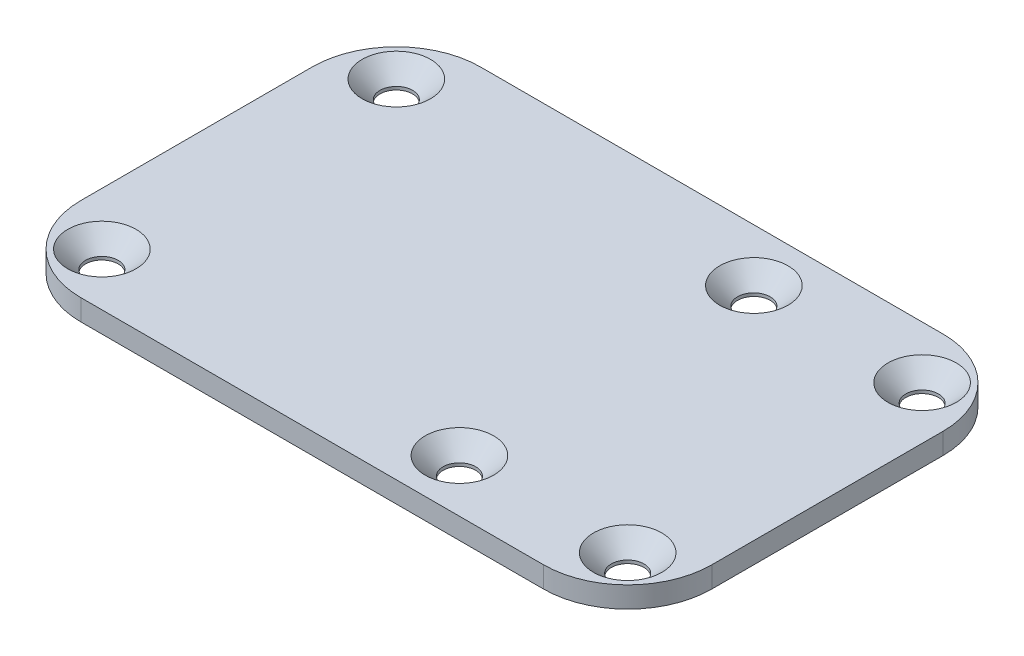
SolidWorks part; units mm, degrees
material "6063-T6"
ref_plane "Front Plane" through (0, 0, 0) normal (0, 0, 1) x (1, 0, 0)
ref_plane "Top Plane" through (0, 0, 0) normal (0, 1, 0) x (1, 0, 0)
ref_plane "Right Plane" through (0, 0, 0) normal (1, 0, 0) x (0, 0, -1)
sketch "Sketch1" plane through (0, 0, 0) normal (0, 1, 0) x (1, 0, 0)
  line L1 (22, -19) -> (-22, -19)
  line L2 (30, -11) -> (30, 11)
  line L3 (22, 19) -> (-22, 19)
  line L4 (-30, -11) -> (-30, 11)
  line L5 (30, -19) -> (-30, 19) construction
  line L6 (30, 19) -> (-30, -19) construction
  arc A0 (30, 11) -> (22, 19) centre (22, 11) ccw
  arc A1 (22, -19) -> (30, -11) centre (22, -11) ccw
  arc A2 (-22, -19) -> (-30, -11) centre (-22, -11) cw
  arc A3 (-22, 19) -> (-30, 11) centre (-22, 11) ccw
  point P0 (0, 0)
  dimension "D3" = 8
  dimension "D1" = 60
  dimension "D2" = 38
extrude "Base" add sketch "Sketch1" along normal blind 2
hole_wizard "Ø3.1 (3.1) Diameter Hole1" positions "Location" profile "Hole" hole size "Ø3.1" standard "ANSI Metric" end condition through all
sketch "Location" plane through (0, 2, 0) normal (0, -1, 0) x (-1, 0, 0)
  line L4 (-33.1926, 0) -> (33.4931, 0) construction
  line L6 (0, 17.9223) -> (0, -17.6691) construction
  point P0 (-25, 14)
  point P2 (-25, -14)
  point P4 (25, -14)
  point P6 (25, 14)
  point P29 (-9, 14)
  point P31 (-9, -14)
  dimension "D1" = 28
  dimension "D2" = 25
  dimension "D3" = 25
  dimension "D4" = 16
sketch "Hole" plane through (25, 2, -14) normal (1, 0, 0) x (0, 0, 1)
  line L0 (0, 0) -> (0, 2)
  line L1 (0, 2) -> (1.55, 2)
  line L2 (1.55, 2) -> (1.55, 1.7)
  line L3 (1.55, 1.7) -> (3.25, 0)
  line L5 (3.25, 0) -> (0, 0)
  line L6 (-1.55, 1.7) -> (-3.25, 0) construction
  line L11 (0, -6.35) -> (0, 107.95) construction
  dimension "Thru Hole Dia." = 3.1
  dimension "Thru Hole Depth" = 2
  dimension "Near C'Sink Dia." = 6.5
  dimension "Near C'Sink Angle" = 90
